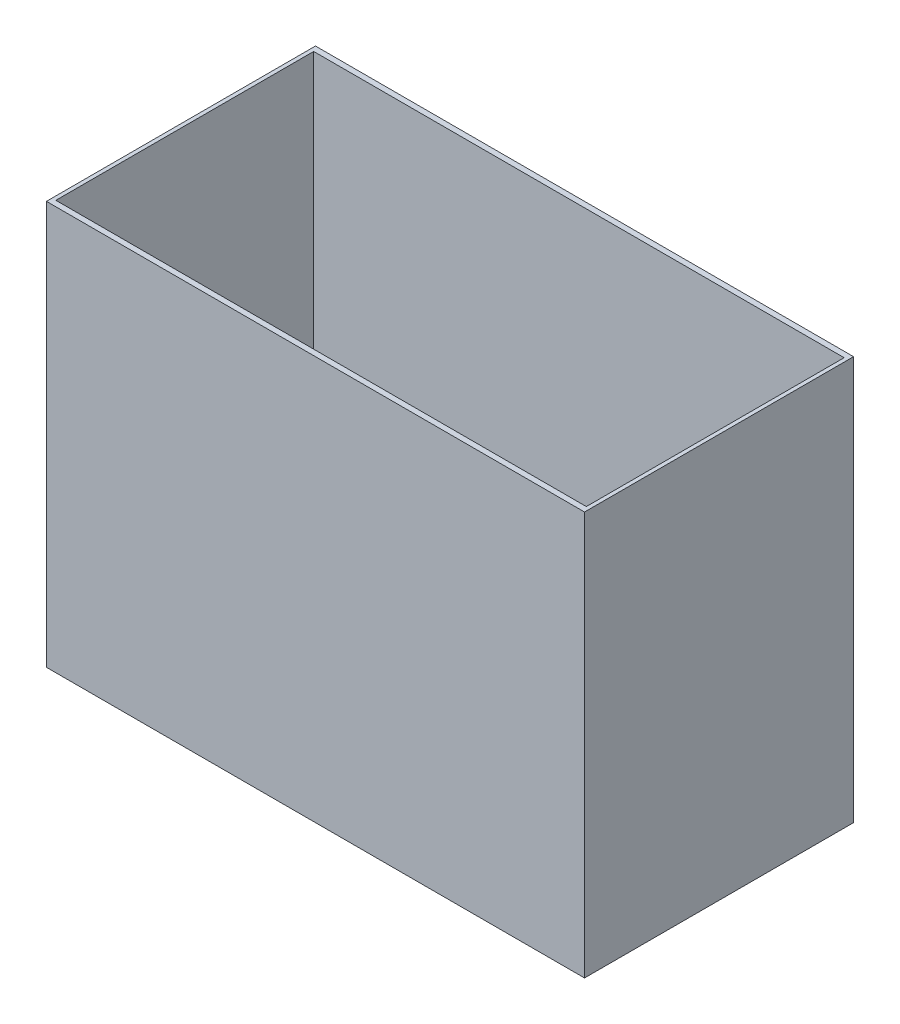
SolidWorks part; units mm, degrees
ref_plane "Front Plane" through (0, 0, 0) normal (0, 0, 1) x (1, 0, 0)
ref_plane "Top Plane" through (0, 0, 0) normal (0, 1, 0) x (1, 0, 0)
ref_plane "Right Plane" through (0, 0, 0) normal (1, 0, 0) x (0, 0, -1)
other "Bounding Box"
ref_plane "Default Plane" through (-292.1, 0, -139.7) normal (0, 1, 0) x (1, 0, 0)
sketch "Sketch1" plane through (0, 0, 0) normal (0, 1, 0) x (1, 0, 0)
  line L0 (-292.1, 0) -> (292.1, 0) construction
  line L1 (-292.1, 139.7) -> (292.1, 139.7)
  line L2 (-292.1, 139.7) -> (-292.1, -139.7)
  line L3 (-292.1, -139.7) -> (292.1, -139.7)
  line L4 (292.1, 139.7) -> (292.1, -139.7)
  line L5 (0, 139.7) -> (0, -139.7) construction
  point P8 (0, 0)
  dimension "D1" = 584.2
  dimension "D2" = 279.4
extrude "Boss-Extrude1" add sketch "Sketch1" along normal blind 6.35
sketch "Sketch2" plane through (0, 6.35, 0) normal (0, 1, 0) x (1, 0, 0)
  line L0 (-245.9259, -63.5) -> (-55.3589, -63.5) construction
  line L1 (-241.3, -120.6497) -> (-152.4, -120.6497)
  line L2 (-241.3, -120.6497) -> (-241.3, -101.5997)
  line L3 (-241.3, -101.5997) -> (-152.4, -101.5997)
  line L4 (-152.4, -120.6497) -> (-152.4, -101.5997)
  line L5 (-241.3, -120.6497) -> (-152.4, -101.5997) construction
  line L6 (-241.3, -101.5997) -> (-152.4, -120.6497) construction
  line L7 (-292.1, 139.7) -> (-292.1, -139.7) construction
  line L8 (-292.1, 0) -> (292.1, 0) construction
  line L9 (292.1, -139.7) -> (292.1, 139.7) construction
  line L10 (0, 0) -> (0, 121.6784) construction
  line L11 (241.3, -101.5997) -> (152.4, -120.6497) construction
  line L12 (241.3, -120.6497) -> (152.4, -101.5997) construction
  line L13 (152.4, -120.6497) -> (152.4, -101.5997)
  line L14 (241.3, -101.5997) -> (152.4, -101.5997)
  line L15 (241.3, -120.6497) -> (241.3, -101.5997)
  line L16 (241.3, -120.6497) -> (152.4, -120.6497)
  point P0 (-196.85, -111.1247)
  point P17 (196.85, -111.1247)
  dimension "D1" = 19.05
  dimension "D2" = 88.9
  dimension "D3" = 38.0997
  dimension "D4" = 50.8
  dimension "D5" = 63.5
extrude "Boss-Extrude2" [suppressed] add sketch "Sketch2" along normal blind 304.8 separate body contours L2 L1 L4 L3
pattern_linear "LPattern1" [suppressed] count 2 spacing 304.8 of bodies 101
pattern_linear "LPattern2" [suppressed] count 2 spacing 215.9 of bodies 101
sketch "Sketch3" plane through (0, 0, 0) normal (0, 1, 0) x (1, 0, 0)
  line L1 (-304.8, -152.4) -> (304.8, -152.4)
  line L2 (-304.8, -152.4) -> (-304.8, 152.4)
  line L3 (-304.8, 152.4) -> (304.8, 152.4)
  line L4 (304.8, -152.4) -> (304.8, 152.4)
  line L5 (-304.8, -152.4) -> (304.8, 152.4) construction
  line L6 (-304.8, 152.4) -> (304.8, -152.4) construction
  line L7 (-300.482, -146.05) -> (300.482, -146.05)
  line L8 (-300.482, -146.05) -> (-300.482, 146.05)
  line L9 (-300.482, 146.05) -> (300.482, 146.05)
  line L10 (300.482, -146.05) -> (300.482, 146.05)
  line L11 (-300.482, -146.05) -> (300.482, 146.05) construction
  line L12 (-300.482, 146.05) -> (300.482, -146.05) construction
  point P0 (0, 0)
  point P6 (0, 0)
  dimension "D1" = 609.6
  dimension "D2" = 304.8
  dimension "D3" = 292.1
  dimension "D4" = 600.964
extrude "Boss-Extrude3" add sketch "Sketch3" along normal blind 457.2 separate body
sketch "Sketch4" plane through (0, 6.35, 0) normal (0, 1, 0) x (1, 0, 0)
  line L0 (292.1, -139.7) -> (292.1, 139.7) construction
  line L1 (238.8561, 120.65) -> (261.8611, 120.65) construction
  line L2 (273.05, 95.4723) -> (273.05, 121.6668) construction
  line L3 (292.1, 139.7) -> (-292.1, 139.7) construction
  circle A3 centre (252.0119, 99.6119) radius 21.0381
  dimension "D1" = 42.0762
  dimension "D2" = 19.05
  dimension "D3" = 19.05
extrude "Cut-Extrude1" cut sketch "Sketch4" against normal through all
sketch "Sketch7" plane through (0, 6.35, 0) normal (0, 1, 0) x (1, 0, 0)
  line L0 (292.1, 0) -> (49.4912, 0) construction
  line L1 (292.1, -139.7) -> (292.1, 139.7) construction
  circle A0 centre (190.5, 0) radius 4 construction
  circle A1 centre (190.5, 0) radius 2.7781
  dimension "D1" = 8
  dimension "D2" = 5.5562
  dimension "D3" = 101.6
extrude "Cut-Extrude3" [suppressed] cut sketch "Sketch7" against normal through all
sketch "Sketch8" [suppressed] plane through (0, 6.35, 0) normal (0, 1, 0) x (1, 0, 0)
  circle A0 centre (94.9, -12.8415) radius 1.9844 construction
  circle A1 centre (146.1, -12.8415) radius 1.9844 construction
  circle A2 centre (146.1, 12.8415) radius 1.9844 construction
  circle A3 centre (94.9, 12.8415) radius 1.9844 construction
  circle A4 centre (94.9, -12.8415) radius 1.9844
  circle A5 centre (146.1, -12.8415) radius 1.9844
  circle A6 centre (146.1, 12.8415) radius 1.9844
  circle A7 centre (94.9, 12.8415) radius 1.9844
extrude "Cut-Extrude4" [suppressed] cut sketch "Sketch8" against normal through all
sketch "Sketch9" plane through (0, 0, 0) normal (0, -1, 0) x (1, 0, 0)
  circle A1 centre (190.5, 0) radius 6.35
  circle A2 centre (146.1, 12.8415) radius 6.35
  circle A3 centre (94.9, 12.8415) radius 6.35
  circle A4 centre (94.9, -12.8415) radius 6.35
  circle A5 centre (146.1, -12.8415) radius 6.35
sketch "Sketch11" plane through (0, 0, 0) normal (0, -1, 0) x (1, 0, 0)
  line L0 (-292.1, 139.7) -> (292.1, 139.7) construction
  line L1 (215.9, 139.7) -> (165.1, 139.7)
  line L2 (215.9, 139.7) -> (215.9, 136.525)
  line L3 (215.9, 136.525) -> (165.1, 136.525)
  line L4 (165.1, 139.7) -> (165.1, 136.525)
  line L5 (292.1, 139.7) -> (292.1, -139.7) construction
  dimension "D1" = 3.175
  dimension "D2" = 50.8
  dimension "D3" = 76.2
extrude "Cut-Extrude6" cut sketch "Sketch11" against normal through all
mirror "Mirror2" about plane through (0, 0, 0) normal (0, 0, 1) of "Cut-Extrude1", "Cut-Extrude6"
sketch "Sketch12" plane through (0, 6.35, 0) normal (0, 1, 0) x (1, 0, 0)
  line L0 (292.1, -17.78) -> (285.75, -17.78) construction
  line L1 (292.1, -43.18) -> (285.75, -43.18) construction
  line L2 (285.75, -43.18) -> (285.75, -17.78) construction
  line L3 (292.1, -78.74) -> (285.75, -78.74) construction
  line L4 (292.1, -104.14) -> (285.75, -104.14) construction
  line L5 (285.75, -78.74) -> (285.75, -104.14) construction
  line L6 (292.1, -17.78) -> (285.75, -17.78)
  line L7 (292.1, -43.18) -> (285.75, -43.18)
  line L8 (285.75, -43.18) -> (285.75, -17.78)
  line L9 (292.1, -78.74) -> (285.75, -78.74)
  line L10 (292.1, -104.14) -> (285.75, -104.14)
  line L11 (285.75, -78.74) -> (285.75, -104.14)
  line L12 (292.1, 0) -> (-292.1, 0) construction
  line L13 (285.75, 78.74) -> (285.75, 104.14)
  line L14 (292.1, 104.14) -> (285.75, 104.14)
  line L15 (292.1, 78.74) -> (285.75, 78.74)
  line L16 (285.75, 43.18) -> (285.75, 17.78)
  line L17 (292.1, 43.18) -> (285.75, 43.18)
  line L18 (292.1, 17.78) -> (285.75, 17.78)
  line L19 (292.1, -139.7) -> (292.1, 139.7) construction
  line L20 (292.1, -104.14) -> (292.1, -78.74)
  line L21 (292.1, -43.18) -> (292.1, -17.78)
  line L22 (292.1, 17.78) -> (292.1, 43.18)
  line L23 (292.1, 78.74) -> (292.1, 104.14)
  line L24 (-292.1, 139.7) -> (-292.1, -139.7) construction
  line L25 (0, 0) -> (0, 121.3012) construction
  line L26 (-292.1, 78.74) -> (-292.1, 104.14)
  line L27 (-292.1, 17.78) -> (-292.1, 43.18)
  line L28 (-292.1, -43.18) -> (-292.1, -17.78)
  line L29 (-292.1, -104.14) -> (-292.1, -78.74)
  line L30 (-292.1, 17.78) -> (-285.75, 17.78)
  line L31 (-292.1, 43.18) -> (-285.75, 43.18)
  line L32 (-285.75, 43.18) -> (-285.75, 17.78)
  line L33 (-292.1, 78.74) -> (-285.75, 78.74)
  line L34 (-292.1, 104.14) -> (-285.75, 104.14)
  line L35 (-285.75, 78.74) -> (-285.75, 104.14)
  line L36 (-285.75, -78.74) -> (-285.75, -104.14)
  line L37 (-292.1, -104.14) -> (-285.75, -104.14)
  line L38 (-292.1, -78.74) -> (-285.75, -78.74)
  line L39 (-285.75, -43.18) -> (-285.75, -17.78)
  line L40 (-292.1, -43.18) -> (-285.75, -43.18)
  line L41 (-292.1, -17.78) -> (-285.75, -17.78)
extrude "Cut-Extrude7" cut sketch "Sketch12" against normal through all
sketch "Sketch13" plane through (0, 6.35, 0) normal (0, 1, 0) x (1, 0, 0)
  line L0 (252.0119, -99.6119) -> (133.5003, -46.1866) construction
  line L1 (210.6176, 12.194) -> (133.5003, -46.1866) construction
  line L2 (252.0119, 99.6119) -> (210.6176, 12.194) construction
  line L3 (257.6906, -66.7163) -> (23.4514, -66.7163) construction
  circle A0 centre (252.0119, -99.6119) radius 21.0381 construction
  circle A1 centre (252.0119, -99.6119) radius 21.0381 construction
  circle A2 centre (133.5003, -46.1866) radius 21.0381
  circle A3 centre (210.6176, 12.194) radius 21.0381
  circle A4 centre (252.0119, 99.6119) radius 21.0381 construction
  circle A5 centre (252.0119, 99.6119) radius 21.0381 construction
  circle A6 centre (210.6176, 12.194) radius 55.7022 construction
  point P9 (0, 0)
  dimension "D1" = 96.7232
  dimension "D3" = 111.4044
extrude "Cut-Extrude8" cut sketch "Sketch13" against normal through all
sketch "Sketch14" plane through (0, 6.35, 0) normal (0, 1, 0) x (1, 0, 0)
  circle A1 centre (45.3035, 4.219) radius 4.7113 construction
  circle A2 centre (45.3035, 4.219) radius 2.7781
  dimension "D1" = 5.5562
extrude "Cut-Extrude9" cut sketch "Sketch14" against normal through all
sketch "Sketch15" plane through (0, 0, 0) normal (0, -1, 0) x (1, 0, 0)
  line L0 (88.9, -38.1) -> (88.9, -57.15) construction
  line L1 (88.9, -57.15) -> (95.25, -57.15) construction
  line L2 (95.25, -57.15) -> (95.25, -38.1) construction
  line L3 (95.25, -38.1) -> (88.9, -38.1) construction
  line L4 (88.9, 57.15) -> (88.9, 31.75) construction
  line L5 (88.9, 31.75) -> (95.25, 31.75) construction
  line L6 (95.25, 31.75) -> (95.25, 57.15) construction
  line L7 (95.25, 57.15) -> (88.9, 57.15) construction
  line L8 (88.9, -38.1) -> (88.9, -57.15) construction
  line L9 (88.9, -57.15) -> (95.25, -57.15) construction
  line L10 (95.25, -57.15) -> (95.25, -38.1) construction
  line L11 (95.25, -38.1) -> (88.9, -38.1) construction
  line L12 (88.9, 57.15) -> (88.9, 31.75) construction
  line L13 (88.9, 31.75) -> (95.25, 31.75) construction
  line L14 (95.25, 31.75) -> (95.25, 57.15) construction
  line L15 (95.25, 57.15) -> (88.9, 57.15) construction
  line L16 (88.773, -37.973) -> (88.773, -57.277)
  line L17 (88.773, -57.277) -> (95.377, -57.277)
  line L18 (95.377, -57.277) -> (95.377, -37.973)
  line L19 (95.377, -37.973) -> (88.773, -37.973)
  line L20 (88.773, 57.277) -> (88.773, 31.623)
  line L21 (88.773, 31.623) -> (95.377, 31.623)
  line L22 (95.377, 31.623) -> (95.377, 57.277)
  line L23 (95.377, 57.277) -> (88.773, 57.277)
  dimension "D1" = 0.127
  dimension "D2" = 0.127
extrude "Cut-Extrude10" cut sketch "Sketch15" against normal through all
sketch "Sketch16" plane through (0, 0, 0) normal (0, -1, 0) x (1, 0, 0)
  line L0 (-63.5, -66.675) -> (-63.5, -53.975) construction
  line L1 (-63.5, -53.975) -> (-38.1, -53.975) construction
  line L2 (-38.1, -66.675) -> (-38.1, -53.975) construction
  line L3 (-63.5, -66.675) -> (-38.1, -66.675) construction
  line L4 (-215.9, -66.675) -> (-215.9, -53.975) construction
  line L5 (-241.3, -53.975) -> (-215.9, -53.975) construction
  line L6 (-241.3, -66.675) -> (-241.3, -53.975) construction
  line L7 (-241.3, -66.675) -> (-215.9, -66.675) construction
  line L8 (-63.5, -66.675) -> (-63.5, -53.975)
  line L9 (-63.5, -53.975) -> (-38.1, -53.975)
  line L10 (-38.1, -66.675) -> (-38.1, -53.975)
  line L11 (-63.5, -66.675) -> (-38.1, -66.675)
  line L12 (-215.9, -66.675) -> (-215.9, -53.975)
  line L13 (-241.3, -53.975) -> (-215.9, -53.975)
  line L14 (-241.3, -66.675) -> (-241.3, -53.975)
  line L15 (-241.3, -66.675) -> (-215.9, -66.675)
  line L16 (-292.1, 0) -> (-84.0789, 0) construction
  line L18 (-241.3, 66.675) -> (-215.9, 66.675)
  line L19 (-241.3, 66.675) -> (-241.3, 53.975)
  line L20 (-241.3, 53.975) -> (-215.9, 53.975)
  line L21 (-215.9, 66.675) -> (-215.9, 53.975)
  line L22 (-63.5, 66.675) -> (-38.1, 66.675)
  line L23 (-38.1, 66.675) -> (-38.1, 53.975)
  line L24 (-63.5, 53.975) -> (-38.1, 53.975)
  line L25 (-63.5, 66.675) -> (-63.5, 53.975)
  line L26 (31.4971, -139.7) -> (31.4971, 139.7) construction
  line L27 (165.1, -139.7) -> (-292.1, -139.7) construction
  line L28 (-292.1, 139.7) -> (165.1, 139.7) construction
  point P24 (31.4971, 0)
extrude "Cut-Extrude11" cut sketch "Sketch16" against normal through all
